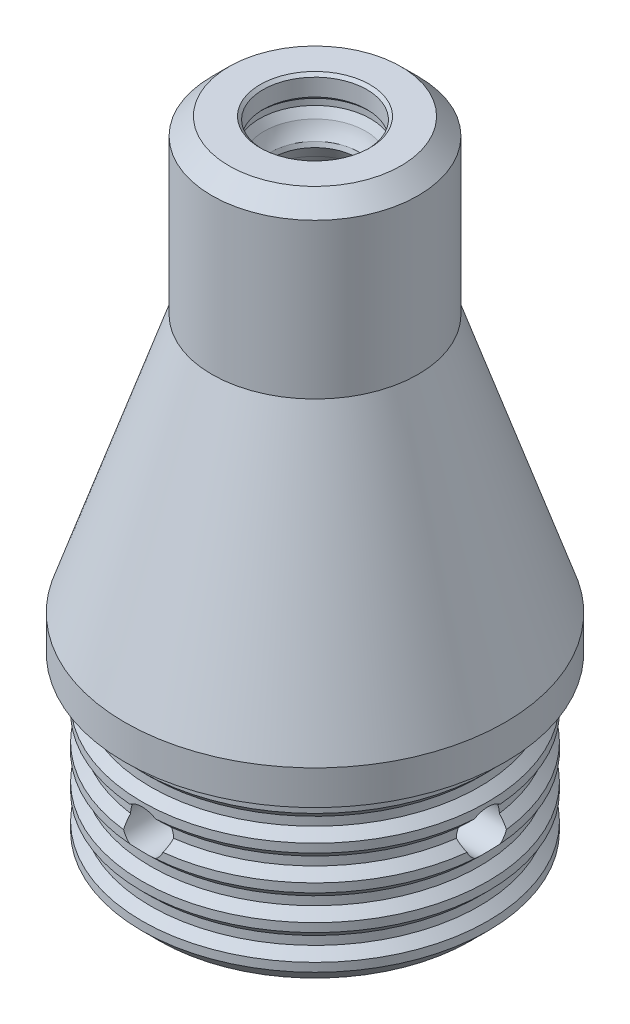
SolidWorks part; units mm, degrees
ref_plane "정면" through (0, 0, 0) normal (0, 0, 1) x (1, 0, 0)
ref_plane "윗면" through (0, 0, 0) normal (0, 1, 0) x (1, 0, 0)
ref_plane "우측면" through (0, 0, 0) normal (1, 0, 0) x (0, 0, -1)
sketch "스케치1" plane through (0, 0, 0) normal (1, 0, 0) x (0, 0, -1)
  line L0 (0, 0) -> (4.2, 0) construction
  line L1 (4.2, 0) -> (4.2, 1)
  line L2 (3.1896, 35) -> (6, 35)
  line L3 (6, 35) -> (6, 25)
  line L4 (6, 25) -> (11.05, 10)
  line L5 (11.05, 10) -> (11.05, 8)
  line L6 (10, 0) -> (4.2, 0) construction
  line L7 (10.05, 7) -> (9.55, 6.5)
  line L8 (9.55, 6.5) -> (9.55, 6)
  line L9 (0, 0) -> (0, 33.7416) construction
  line L10 (11.05, 8) -> (10.05, 8)
  line L11 (10.05, 8) -> (10.05, 7)
  line L12 (10.05, 5.5) -> (10.05, 5)
  line L13 (3.1896, 35) -> (3.02, 34.8304)
  line L14 (3.02, 34.8304) -> (3.02, 33.8304)
  line L15 (2.3992, 31.7786) -> (2.8027, 31)
  line L16 (3.02, 33.8304) -> (3.23, 33.6204)
  line L17 (4.2, 2.5) -> (4.7, 2)
  line L18 (4.7, 2) -> (4.7, 1.5)
  line L19 (2.8027, 31) -> (4.2, 31) construction
  line L20 (9.55, 6) -> (10.05, 5.5)
  line L21 (9.55, 4) -> (10.05, 3.5)
  line L22 (9.55, 4.5) -> (9.55, 4)
  line L23 (10.05, 5) -> (9.55, 4.5)
  line L24 (9.55, 2) -> (10.05, 1.5)
  line L25 (9.55, 2.5) -> (9.55, 2)
  line L26 (10.05, 3) -> (9.55, 2.5)
  line L27 (10.05, 3.5) -> (10.05, 3)
  line L28 (10.05, 1.5) -> (10.05, 1)
  line L29 (10.05, -0.5) -> (10.05, -1)
  line L30 (10.05, -1.9994) -> (4.2, -1.9994)
  line L31 (4.2, -1.9994) -> (4.2, 0)
  line L32 (9.55, 0) -> (10.05, -0.5)
  line L33 (9.55, 0.5) -> (9.55, 0)
  line L34 (10.05, 1) -> (9.55, 0.5)
  line L35 (4.7, 1.5) -> (4.2, 1)
  line L36 (4.2, 2.5) -> (4.2, 4)
  line L37 (4.2, 5.5) -> (4.7, 5)
  line L38 (10.05, -1) -> (10.05, -1.9994)
  line L39 (3.23, 33.6204) -> (3.23, 33.2604)
  line L40 (4.2, 31) -> (4.2, 28) construction
  line L41 (4.2, 28) -> (3.5337, 29.4305)
  line L42 (3.5337, 29.4305) -> (2.8027, 31)
  line L43 (3.23, 33.2604) -> (2.9466, 32.7786)
  line L44 (9.55, -2) -> (10.05, -2.5) [skipped]
  line L45 (9.55, -1.5) -> (9.55, -2) [skipped]
  line L46 (10.05, -1) -> (9.55, -1.5) [skipped]
  line L47 (4.7, 5) -> (4.7, 4.5)
  line L48 (4.7, 4.5) -> (4.2, 4)
  line L49 (4.2, 8.5) -> (4.7, 8)
  line L50 (4.7, 8) -> (4.7, 7.5)
  line L51 (4.7, 7.5) -> (4.2, 7)
  line L52 (4.2, 11.5) -> (4.7, 11)
  line L53 (4.7, 11) -> (4.7, 10.5)
  line L54 (4.7, 10.5) -> (4.2, 10)
  line L55 (4.2, 14.5) -> (4.7, 14)
  line L56 (4.7, 14) -> (4.7, 13.5)
  line L57 (4.7, 13.5) -> (4.2, 13)
  line L58 (4.2, 14.5) -> (4.2, 28)
  line L59 (4.2, 11.5) -> (4.2, 13)
  line L60 (4.2, 8.5) -> (4.2, 10)
  line L61 (4.2, 5.5) -> (4.2, 7)
  circle A1 centre (0, 33.7416) radius 3 construction
  arc A2 (2.3992, 31.7786) -> (2.9466, 32.7786) centre (0, 33.7416) ccw
  dimension "D10" = 0.5
  dimension "D13" = 6
  dimension "D14" = 31
  dimension "D17" = 3.1
  dimension "D1" = 10
  dimension "D2" = 2
  dimension "D3" = 3
  dimension "D4" = 15
  dimension "D5" = 10.05
  dimension "D6" = 4.2
  dimension "D7" = 1
  dimension "D8" = 6
  dimension "D9" = 10
  dimension "D11" = 1.5
  dimension "D12" = 1
  dimension "D15" = 3.02
  dimension "D16" = 135
  dimension "D18" = 135
  dimension "D19" = 0.5
  dimension "D20" = 1.5
  dimension "D21" = 1
  dimension "D22" = 0.5
  dimension "D23" = 5
  dimension "D24" = 1
  dimension "D25" = 2
  dimension "D27" = 0.5
  dimension "D28" = 28
  dimension "D26" = 3
revolve "회전1" add sketch "스케치1" angle 360 about L9
chamfer "모따기1" distance 1 angle 45 2 edges at (0, 35, -6) (0, -1.9994, -4.2)
chamfer "모따기2" distance 0.1 angle 45 1 edges at (0, 31.7786, -2.3992) first distance on face at (0, 31, -2.8027)
chamfer "모따기3" distance 1 angle 45 1 edges at (0, -1.9994, -10.05)
ref_plane "평면1" through (-11.05, 0, 0) normal (-1, 0, 0) x (0, 0, 1)
sketch "스케치2" plane through (-11.05, 0, 0) normal (-1, 0, 0) x (0, 0, 1)
  line L0 (0, 4) -> (0, 0) construction
  circle A0 centre (0, 4) radius 1.25
  dimension "D1" = 2.5
  dimension "D2" = 4
extrude "컷-돌출1" cut sketch "스케치2" against normal blind 5
pattern_circular "원형 패턴1" count 4 over 360 about axis through (0, 0, 0) along (0, -1, 0) of "컷-돌출1"
chamfer "모따기4" distance 0.5 angle 45 4 edges at (6.05, 4, -1.25) (-1.25, 4, -6.05) (-6.05, 4, 1.25) (1.25, 4, 6.05)
